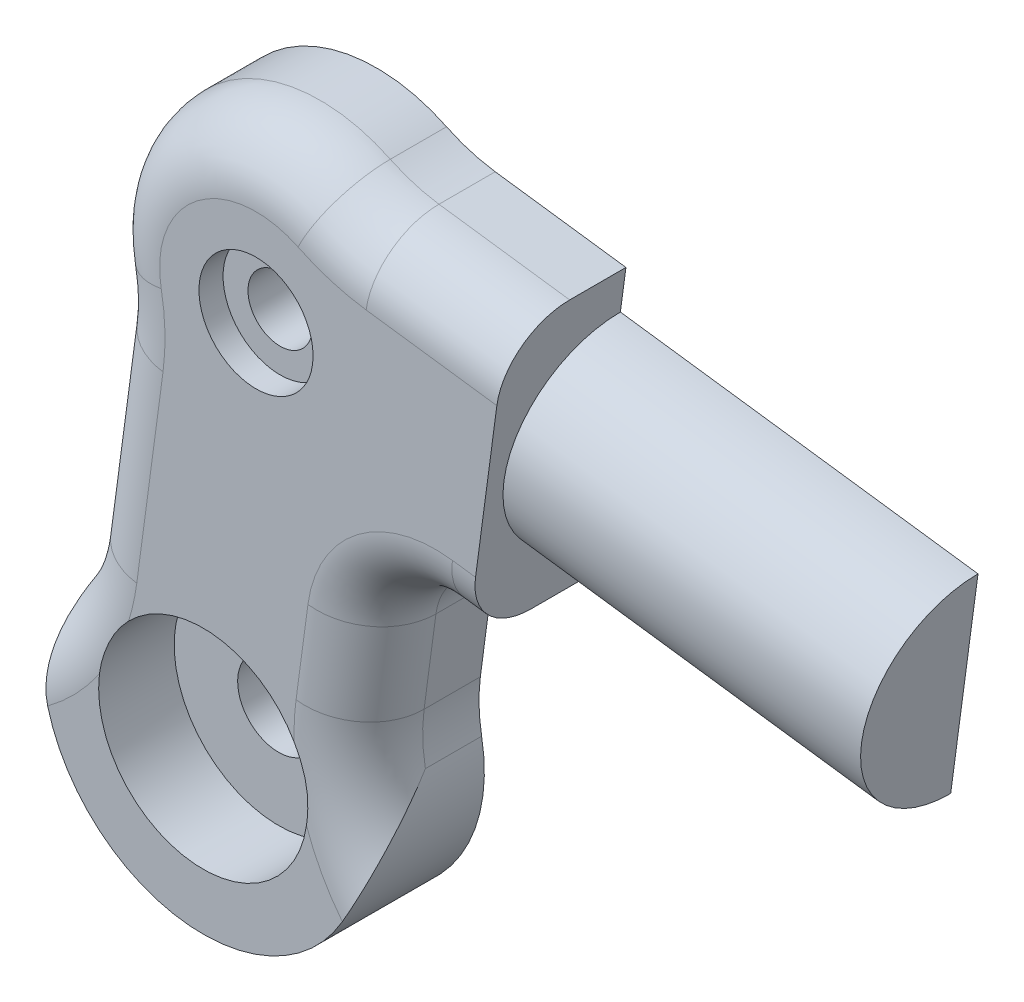
SolidWorks part; units mm, degrees
ref_plane "前视基准面" through (0, 0, 0) normal (0, 0, 1) x (1, 0, 0)
ref_plane "上视基准面" through (0, 0, 0) normal (0, 1, 0) x (1, 0, 0)
ref_plane "右视基准面" through (0, 0, 0) normal (1, 0, 0) x (0, 0, -1)
sketch "草图4" plane through (0, 0, 0) normal (0, 0, 1) x (1, 0, 0)
  arc B0 (4.3559, 9.0014) -> (-9.499, -3.1256) centre (0, 0) ccw
  arc B1 (4.3559, 9.0014) -> (7.3844, 8.0914) centre (8.7119, 18.0029) ccw
  line B2 (15.5168, 7.0022) -> (7.3844, 8.0914)
  line B3 (13.1274, -10.8385) -> (15.5168, 7.0022)
  arc B4 (11.6903, -10.646) -> (7.1947, -14.0796) centre (11.1593, -14.6106) ccw
  line B5 (11.6903, -10.646) -> (13.1274, -10.8385)
  circle B6 centre (0, 0) radius 2.55
  line B7 (6.4573, -19.5857) -> (7.1947, -14.0796)
  arc B8 (6.4573, -19.5857) -> (6.5384, -22.7469) centre (16.3688, -20.9131) ccw
  arc B9 (-12.2935, -20.2248) -> (6.5384, -22.7469) centre (-3.2921, -24.5807) ccw
  arc B10 (-3.2334, -18.081) -> (-1.6383, -18.2946) centre (-3.2921, -24.5807) ccw construction
  circle B11 centre (-3.2921, -24.5807) radius 2.55
  line B12 (-9.499, -3.1256) -> (-11.3834, -17.1963)
  arc B13 (-12.2935, -20.2248) -> (-11.3834, -17.1963) centre (-21.2949, -15.8689) ccw
  line B14 (37.423, 1.4451) -> (15.1717, 4.4252)
  line B15 (-1.6383, -18.2946) -> (-3.2334, -18.081) construction
  line B16 (13.4726, -8.2615) -> (35.7239, -11.2416)
  line B17 (35.7239, -11.2416) -> (37.423, 1.4451)
sketch_block_instance "块2-1"
sketch_block "块2"
sketch "草图5" plane through (0, 0, 0) normal (0, 0, 1) x (1, 0, 0)
  line L0 (15.5168, 7.0022) -> (7.3844, 8.0914) construction
  line L1 (13.1274, -10.8385) -> (15.5168, 7.0022) construction
  line L2 (11.6903, -10.646) -> (13.1274, -10.8385) construction
  line L3 (6.4573, -19.5857) -> (7.1947, -14.0796) construction
  line L4 (-9.499, -3.1256) -> (-11.3834, -17.1963) construction
  line L5 (15.5168, 7.0022) -> (7.3844, 8.0914)
  line L6 (13.1274, -10.8385) -> (15.5168, 7.0022)
  line L7 (11.6903, -10.646) -> (13.1274, -10.8385)
  line L8 (6.4573, -19.5857) -> (7.1947, -14.0796)
  line L9 (-9.7493, -4.995) -> (-11.3834, -17.1963)
  arc A0 (4.3559, 9.0014) -> (-9.499, -3.1256) centre (0, 0) ccw construction
  arc A1 (4.3559, 9.0014) -> (7.3844, 8.0914) centre (8.7119, 18.0029) ccw construction
  arc A2 (11.6903, -10.646) -> (7.1947, -14.0796) centre (11.1593, -14.6106) ccw construction
  arc A4 (6.4573, -19.5857) -> (6.5384, -22.7469) centre (16.3688, -20.9131) ccw construction
  arc A5 (-12.2935, -20.2248) -> (6.5384, -22.7469) centre (-3.2921, -24.5807) ccw construction
  circle A6 centre (-3.2921, -24.5807) radius 2.55 construction
  arc A7 (-12.2935, -20.2248) -> (-11.3834, -17.1963) centre (-21.2949, -15.8689) ccw construction
  arc A8 (4.3559, 9.0014) -> (-9.8304, -1.8338) centre (0, 0) ccw
  arc A9 (4.3559, 9.0014) -> (7.3844, 8.0914) centre (8.7119, 18.0029) ccw
  arc A10 (11.6903, -10.646) -> (7.1947, -14.0796) centre (11.1593, -14.6106) ccw
  circle A11 centre (0, 0) radius 2
  arc A12 (6.4573, -19.5857) -> (6.5384, -22.7469) centre (16.3688, -20.9131) ccw
  arc A13 (-12.2935, -20.2248) -> (6.5384, -22.7469) centre (-3.2921, -24.5807) ccw
  circle A14 centre (-3.2921, -24.5807) radius 2.55
  arc A15 (-12.2935, -20.2248) -> (-11.3834, -17.1963) centre (-21.2949, -15.8689) ccw
  arc A16 (-9.8304, -1.8338) -> (-9.7493, -4.995) centre (-19.6608, -3.6676) cw
  dimension "D1" = 10
  dimension "D2" = 4
extrude "凸台-拉伸3" add sketch "草图5" along normal blind 15
fillet "圆角4" radius 4 15 edges at (5.834, 8.4259, 0) (11.4506, 7.5468, 0) (-6.0699, 7.9471, 0) (-9.6641, -3.4112, 0) (-10.5664, -11.0957, 0) (-11.718, -18.7468, 0) (6.3721, -21.1695, 0) (6.826, -16.8327, 0) (12.4088, -10.7423, 0) (6.826, -16.8327, 15) (6.3721, -21.1695, 15) (12.4088, -10.7423, 15) (-10.5664, -11.0957, 15) (-11.718, -18.7468, 15) (11.4506, 7.5468, 15)
sketch "草图6" plane through (14.3221, -1.9181, 0) normal (0.9912, -0.1327, 0) x (0, 0, -1)
  line L0 (-15, -5) -> (-15, 5) construction
  line L1 (-11, 9) -> (-4, 9) construction
  circle A0 centre (-7.5, 0) radius 6.4
  dimension "D3" = 12.8
  dimension "D1" = 7.5
  dimension "D2" = 9
extrude "凸台-拉伸4" add sketch "草图6" along normal up to vertex (22.45 mm away)
sketch "草图7" plane through (0, 0, 15) normal (0, 0, 1) x (1, 0, 0)
  circle A0 centre (-3.2921, -24.5807) radius 6.5
extrude "切除-拉伸1" cut sketch "草图7" against normal blind 4.7
sketch "草图8" plane through (0, 0, 0) normal (0, 0, -1) x (-1, 0, 0)
  circle A0 centre (3.2921, -24.5807) radius 6.5
extrude "切除-拉伸2" cut sketch "草图8" against normal blind 4.7
sketch "草图9" plane through (36.5735, -4.8982, 0) normal (0.9912, -0.1327, 0) x (0, 0, -1)
  line L1 (-7.5, 15.1998) -> (0, 15.1998)
  line L2 (-7.5, 15.1998) -> (-7.5, -34.8002)
  line L3 (-7.5, -34.8002) -> (0, -34.8002)
  line L4 (0, 15.1998) -> (0, -34.8002)
  dimension "D1" = 7.5
  dimension "D2" = 50
extrude "切除-拉伸3" cut sketch "草图9" against normal through all
sketch "草图10" plane through (0, 0, 15) normal (0, 0, 1) x (1, 0, 0)
  circle A0 centre (0, 0) radius 3.55
  dimension "D1" = 7.1
extrude "切除-拉伸4" cut sketch "草图10" against normal blind 1.5
